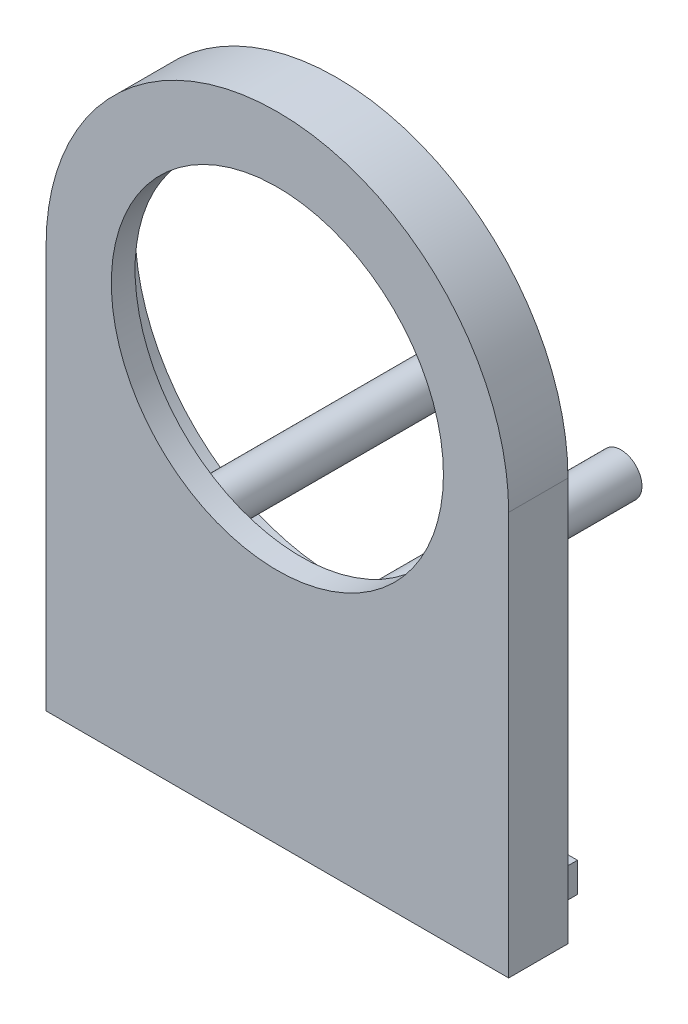
SolidWorks part; units mm, degrees
ref_plane "Front Plane" through (0, 0, 0) normal (0, 0, 1) x (1, 0, 0)
ref_plane "Top Plane" through (0, 0, 0) normal (0, 1, 0) x (1, 0, 0)
ref_plane "Right Plane" through (0, 0, 0) normal (1, 0, 0) x (0, 0, -1)
sketch "Sketch1" plane through (0, 0, 0) normal (0, 0, 1) x (1, 0, 0)
  circle A0 centre (0, 0) radius 35.56
  circle A1 centre (0, 0) radius 43.18
  circle A2 centre (0, 0) radius 49.53
extrude "Boss-Extrude1" add sketch "Sketch1" against normal blind 5.08 contours A1 A0 region at (-41.9587, 0, 0)
extrude "Boss-Extrude2" add sketch "Sketch1<4>" against normal blind 12.7 contours A2 A1 region at (-48.1291, 0, 0)
sketch "Sketch1<4>" plane through (0, 0, 0) normal (0, 0, 1) x (1, 0, 0) same geometry as "Sketch1"
sketch "Sketch2" plane through (0, 0, 0) normal (0, 0, 1) x (1, 0, 0)
  line L2 (-49.53, 0) -> (-49.53, -49.53)
  line L7 (0, -86.36) -> (-49.53, -86.36)
  line L8 (-49.53, -86.36) -> (-49.53, -49.53)
  line L10 (49.53, 0) -> (49.53, -86.36)
  line L11 (49.53, -86.36) -> (0, -86.36)
  circle A0 centre (0, 0) radius 49.53 construction
  circle A2 centre (0, 0) radius 49.53
  circle M8 centre (0, 0) radius 49.53
extrude "Boss-Extrude3" add sketch "Sketch2" against normal blind 12.7 contours L11 L10 L2 L8 L7 M8 region at (0, -61.3429, 0)
sketch "Sketch3" plane through (-49.53, 0, 0) normal (-1, 0, 0) x (0, 0, 1)
  line L0 (0, -86.36) -> (-22.86, -86.36)
  line L1 (-22.86, -86.36) -> (-22.86, -80.01)
  line L2 (-22.86, -80.01) -> (-12.7, -80.01)
  line L3 (-12.7, 0) -> (-12.7, -86.36) construction
  line L4 (-12.7, -80.01) -> (-12.7, -86.36)
  line M4 (-12.7, 0) -> (-12.7, -86.36)
extrude "Boss-Extrude4" add sketch "Sketch3" against normal blind 90.932 contours L2 L1 L0 M4 region at (-49.53, -83.185, -17.78)
sketch "Sketch4" plane through (0, 0, -12.7) normal (0, 0, -1) x (-1, 0, 0)
  circle A5 centre (-17.6965, -36.7555) radius 4.4954
  circle A6 centre (20.0525, -36.7555) radius 4.4954
extrude "Boss-Extrude5" add sketch "Sketch4" along normal blind 43.18 and the other way blind 8.89
